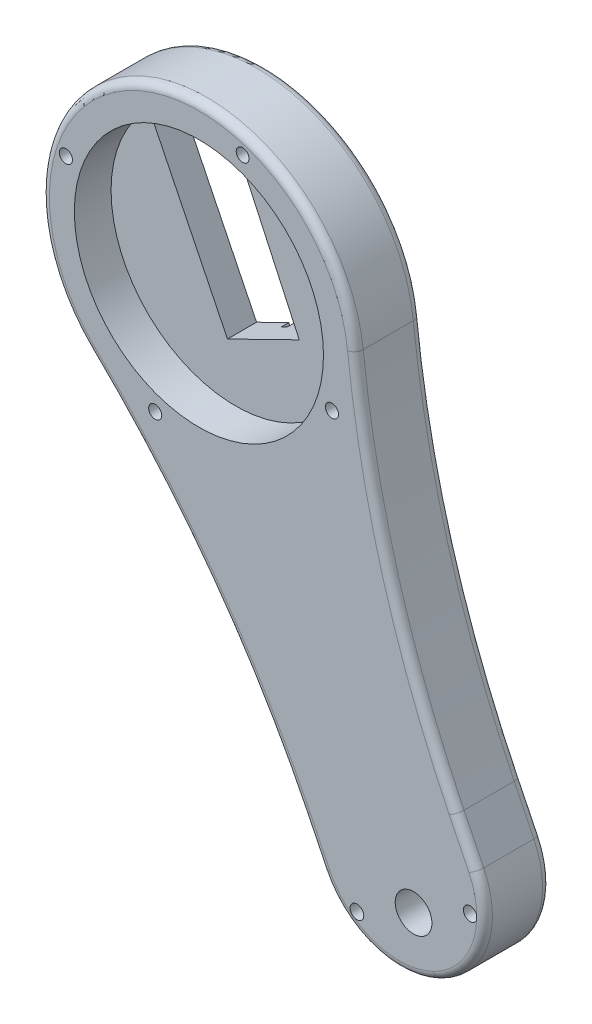
SolidWorks part; units mm, degrees
ref_plane "Front Plane" through (0, 0, 0) normal (0, 0, 1) x (1, 0, 0)
ref_plane "Top Plane" through (0, 0, 0) normal (0, 1, 0) x (1, 0, 0)
ref_plane "Right Plane" through (0, 0, 0) normal (1, 0, 0) x (0, 0, -1)
sketch "Sketch1" plane through (0, 0, 0) normal (0, 0, 1) x (1, 0, 0)
  circle A0 centre (0, 0) radius 60
  dimension "D1" = 120
extrude "Boss-Extrude1" add sketch "Sketch1" along normal blind 25.1
sketch "Sketch2" plane through (0, 0, 25.1) normal (0, 0, 1) x (1, 0, 0)
  circle A0 centre (-16.6647, -50.7331) radius 2.495
  circle A1 centre (-50.7331, 16.6647) radius 2.5
  circle A2 centre (16.6647, 50.7331) radius 2.4444
  circle A3 centre (50.7331, -16.6647) radius 2.5
sketch "Sketch3" plane through (0, 0, 25.1) normal (0, 0, 1) x (1, 0, 0)
  circle A0 centre (0, 0) radius 47.5
  dimension "D1" = 95
extrude "Cut-Extrude2" cut sketch "Sketch3" against normal blind 14
extrude "Cut-Extrude5" cut sketch "Sketch2" against normal through all both and the other way through all
sketch "Sketch6" plane through (0, 0, 0) normal (0, 0, -1) x (-1, 0, 0)
  circle A0 centre (11.9735, 47.2126) radius 3
  circle A1 centre (27.3813, 40.0293) radius 3
  circle A2 centre (-19.7177, -20.7629) radius 3
  circle A3 centre (-4.3099, -27.9462) radius 3
  dimension "D1" = 6
  dimension "D2" = 6
  dimension "D3" = 6
  dimension "D4" = 6
extrude "Cut-Extrude6" cut sketch "Sketch6" against normal blind 6
sketch "Sketch7" plane through (0, 0, 11.1) normal (0, 0, 1) x (1, 0, 0)
  line L0 (-32.4009, 32.8719) -> (-3.109, -26.9124)
  line L1 (-3.109, -26.9124) -> (24.2542, -13.5055)
  line L2 (24.2542, -13.5055) -> (-3.6508, 46.9583)
  line L3 (-3.6508, 46.9583) -> (-32.4009, 32.8719)
  circle A0 centre (0, 0) radius 47.1 construction
extrude "Cut-Extrude7" cut sketch "Sketch7" against normal through all both and the other way through all
ref_plane "Plane1" through (33.538, -68.4503, 0) normal (0.44, -0.898, 0) x (-0.898, -0.44, 0)
sketch "Sketch8" plane through (33.538, -68.4503, 0) normal (0.44, -0.898, 0) x (-0.898, -0.44, 0)
  line L1 (-32.5, 0) -> (32.5, 0)
  line L2 (-32.5, 0) -> (-32.5, -25.1)
  line L3 (-32.5, -25.1) -> (32.5, -25.1)
  line L4 (32.5, 0) -> (32.5, -25.1)
  line L5 (-32.5, 0) -> (32.5, -25.1) construction
  line L6 (-32.5, -25.1) -> (32.5, 0) construction
  point P0 (0, -12.55)
  point P5 (0, 0)
  point P6 (0, 0)
  point P7 (0, 0)
  point P9 (0, 0)
  dimension "D1" = 65
  dimension "D2" = 25.1
extrude "Boss-Extrude2" add sketch "Sketch8" along normal blind 130 and the other way blind 28
sketch "Sketch12" plane through (0, 0, 0) normal (0, 0, -1) x (-1, 0, 0)
  line L0 (16.5698, 40.6285) -> (19.584, 46.7804)
  line L1 (3.6508, 46.9583) -> (32.4009, 32.8719) construction
  line L2 (19.584, 46.7804) -> (22.1828, 45.5071)
  line L3 (22.1828, 45.5071) -> (19.1686, 39.3552)
  line L4 (19.1686, 39.3552) -> (16.5698, 40.6285)
  line L5 (-11.4581, -19.7751) -> (-14.3908, -26.3385)
  line L6 (3.109, -26.9124) -> (-24.2542, -13.5055) construction
  line L7 (-14.3908, -26.3385) -> (-12.0521, -27.3835)
  line L8 (-12.0521, -27.3835) -> (-9.1563, -20.9029)
  line L9 (-9.1563, -20.9029) -> (-11.4581, -19.7751)
extrude "Cut-Extrude9" cut sketch "Sketch12" against normal blind 3
fillet "Fillet6" radius 32.5 2 edges at (61.5511, -199.4905, 12.55) (119.9214, -170.8913, 12.55)
fillet "Fillet7" radius 400 2 edges at (-6.9941, -59.591, 12.55) (51.3761, -30.9918, 12.55)
fillet "Fillet8" radius 3 14 edges at (-26.3992, 53.8803, 0) (3.908, -95.5325, 0) (43.4983, -162.6451, 0) (65.911, -186.7541, 0) (107.185, -166.5314, 0) (101.8686, -134.046, 0) (101.8686, -134.046, 25.1) (107.185, -166.5314, 25.1) (65.911, -186.7541, 25.1) (43.4983, -162.6451, 25.1) (3.908, -95.5325, 25.1) (-26.3992, 53.8803, 25.1) (73.0967, -61.6327, 0) (73.0967, -61.6327, 25.1)
sketch "Sketch14" plane through (0, 0, 25.1) normal (0, 0, 1) x (1, 0, 0)
  line L0 (89.4163, -182.4969) -> (10.5726, -20.209)
  line L1 (-3.109, -26.9124) -> (24.2542, -13.5055) construction
  circle A0 centre (103.4321, -156.4245) radius 2.6
  circle A1 centre (60.2576, -177.3998) radius 2.6
  arc M2 (89.4163, -182.4969) -> (102.9278, -143.0261) centre (76.4367, -156.0058) ccw
  dimension "D1" = 5.2
  dimension "D2" = 24
extrude "Cut-Extrude10" cut sketch "Sketch14" against normal through all both and the other way through all contours A1 | A0 M2 region at (103.4203, -156.4244, 25.1) region at (60.2576, -177.3998, 25.1)
sketch "Sketch15" plane through (0, 0, 25.1) normal (0, 0, 1) x (1, 0, 0)
  circle A0 centre (81.8448, -166.9122) radius 7
  dimension "D1" = 14
extrude "Cut-Extrude11" cut sketch "Sketch15" against normal through all both and the other way through all
